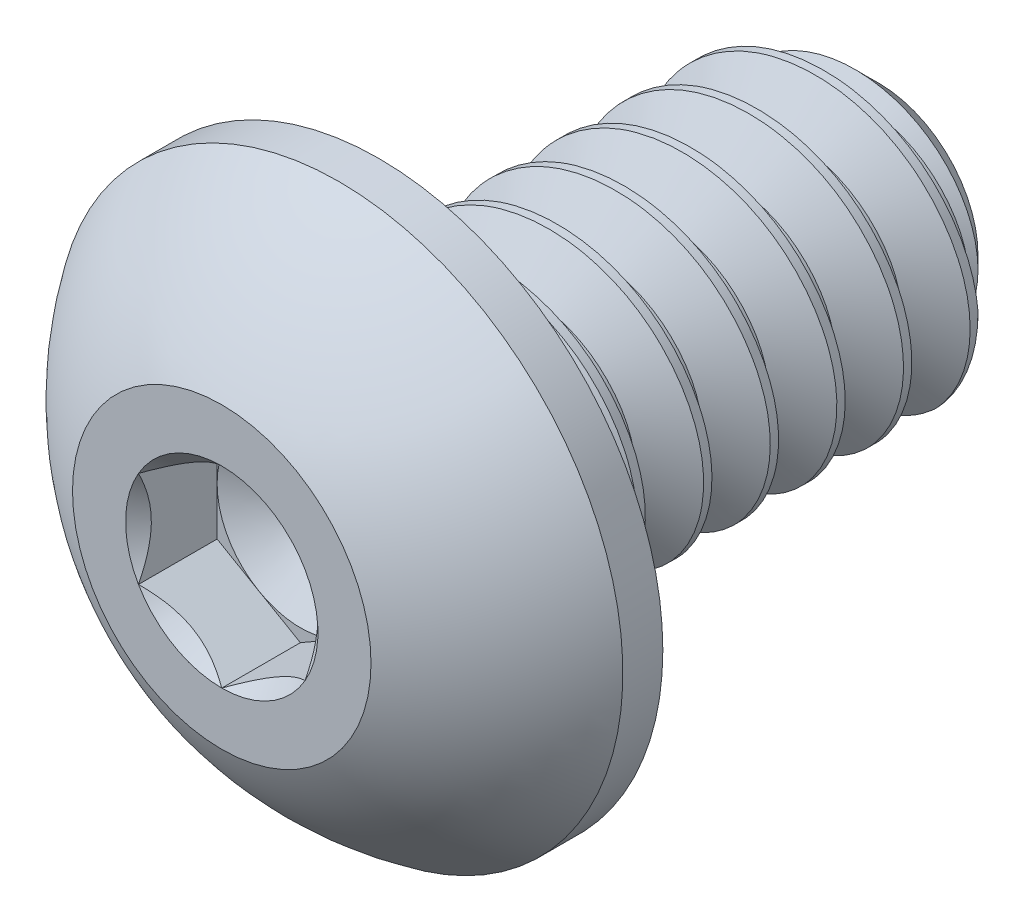
SolidWorks part; units mm, degrees
ref_plane "Front" through (0, 0, 0) normal (0, 0, 1) x (1, 0, 0)
ref_plane "Top" through (0, 0, 0) normal (0, 1, 0) x (1, 0, 0)
ref_plane "Right" through (0, 0, 0) normal (1, 0, 0) x (0, 0, -1)
sketch "Sketch1" plane through (0, 0, 0) normal (1, 0, 0) x (0, 0, -1)
  line L0 (0, 0) -> (-1.4986, 0) construction
  line L1 (0, 0) -> (4.7625, 0)
  line L2 (0, 0) -> (0, 1.4224)
  line L3 (0, 1.4224) -> (4.7625, 1.4224)
  line L4 (4.7625, 0) -> (4.7625, 1.4224)
  line L5 (0, -1.4224) -> (4.7625, -1.4224) construction
  dimension "D1" = 4.7625
  dimension "Thread Dia" = 2.8448
  dimension "Length" = 4.7625
  dimension "Head Height" = 1.4986
revolve "Revolve1" add sketch "Sketch1" angle 360 about L0
ref_plane "Plane1" through (0, 0, 1.4986) normal (0, 0, 1) x (1, 0, 0)
chamfer "Chamfer1" distance 0.4763 angle 45 1 edges at (0, 1.4224, -4.7625)
sketch "Sketch10" plane through (0, 0, 0) normal (1, 0, 0) x (0, 0, -1)
  line L0 (4.7625, 1.4224) -> (5.3181, 1.4224)
  line L1 (5.3181, 1.4224) -> (5.08, 1.01)
  line L2 (5.08, 1.01) -> (5.0006, 1.01)
  line L3 (5.0006, 1.01) -> (4.7625, 1.4224)
  line L4 (4.8816, 1.2162) -> (5.1991, 1.2162) construction
  dimension "D1" = 60
  dimension "D2" = 0.0794
  dimension "D3" = 0.3175
sketch "Sketch11" plane through (0, 0, -4.7625) normal (0, 0, -1) x (-1, 0, 0)
  circle A1 centre (0, 0) radius 0.9462
  circle A2 centre (0, 0) radius 0.9462
  dimension "D1" = 0
curve "Helix/Spiral1" pitch 0.635 height 7.9375 turns 12.5
sweep "Cut-Sweep1" cut profiles "Sketch10" path "Helix/Spiral1"
sketch "Sketch4" plane through (0, 0, 0) normal (0, 0, 1) x (1, 0, 0)
  circle A0 centre (0, 0) radius 2.7051
  dimension "Head Dia" = 5.4102
extrude "Extrude1" add sketch "Sketch4" along normal up to surface (1.4986 mm away) up to plane "Plane1"
sketch "Sketch9" plane through (0, 0, 0) normal (1, 0, 0) x (0, 0, -1)
  line L0 (0, 2.7051) -> (-0.381, 2.7051)
  line L1 (0, 2.7051) -> (0, 3.0861)
  line L2 (0, 3.0861) -> (-1.8796, 3.0861)
  line L3 (0, 0) -> (-1.4986, 0) construction
  line L4 (-1.8796, 3.0861) -> (-1.8796, 1.4224)
  line L5 (-1.8796, 1.4224) -> (-1.4986, 1.4224)
  line L6 (0, 0) -> (0, 1.4224) construction
  line L10 (0, 2.7051) -> (-1.4986, 2.7051) construction
  line L11 (0, 1.4224) -> (4.7625, 1.4224) construction
  line L12 (-1.4986, 2.7051) -> (-1.4986, -2.7051) construction
  arc A0 (-1.4986, 1.4224) -> (-0.381, 2.7051) centre (1.4288, 0) cw
  dimension "Side Head Height" = 0.381
revolve "Cut-Revolve3" cut sketch "Sketch9" angle 360 about L3
sketch "Sketch6" plane through (0, 0, 1.4986) normal (0, 0, 1) x (1, 0, 0)
  line L1 (0, -0.9165) -> (0.7937, -0.4583)
  line L2 (0.7937, -0.4583) -> (0.7937, 0.4583)
  line L3 (0.7937, 0.4583) -> (0, 0.9165)
  line L4 (0, 0.9165) -> (-0.7938, 0.4583)
  line L5 (-0.7938, 0.4583) -> (-0.7938, -0.4583)
  line L6 (-0.7938, -0.4583) -> (0, -0.9165)
  circle A0 centre (0, 0) radius 0.7938 construction
  dimension "Hex" = 1.5875
extrude "Cut-Extrude1" cut sketch "Sketch6" against normal blind 0.7493
sketch "Sketch7" plane through (0, 0, 1.4986) normal (0, 0, 1) x (1, 0, 0)
  circle A0 centre (0, 0) radius 0.9165
extrude "Cut-Extrude4" cut sketch "Sketch7" against normal blind 0.7493 draft 45
sketch "Sketch8" plane through (0, 0, 0.7493) normal (0, 0, 1) x (1, 0, 0)
  circle A0 centre (0, 0) radius 0.7938 construction
  circle A1 centre (0, 0) radius 0.7938
extrude "Cut-Extrude5" cut sketch "Sketch8" against normal blind 0.2498 draft 60
sketch "Sketch12" plane through (0, 0, 0) normal (1, 0, 0) x (0, 0, -1)
  line L1 (0, -1.4224) -> (4.7625, -1.4224) construction
  spline S0 degree 2 poles (4.2862, 0.013) (4.2444, 0.5945) (4.2069, 1.0058) (4.154, 1.5865) (4.101, 1.3739) (4.0481, 1.1614) (3.9952, 0.3681) (3.9423, -0.4251) (3.8894, -1.0058) (3.8365, -1.5865) (3.7835, -1.3739) (3.7306, -1.1614) (3.6777, -0.3681) (3.6248, 0.4251) (3.5719, 1.0058) (3.519, 1.5865) (3.466, 1.3739) (3.4131, 1.1614) (3.3602, 0.3681) (3.3073, -0.4251) (3.2544, -1.0058) (3.2015, -1.5865) (3.1485, -1.3739) (3.0956, -1.1614) (3.0427, -0.3681) (2.9898, 0.4251) (2.9369, 1.0058) (2.884, 1.5865) (2.831, 1.3739) (2.7781, 1.1614) (2.7252, 0.3681) (2.6723, -0.4251) (2.6194, -1.0058) (2.5665, -1.5865) (2.5135, -1.3739) (2.4606, -1.1614) (2.4077, -0.3681) (2.3548, 0.4251) (2.3019, 1.0058) (2.249, 1.5865) (2.196, 1.3739) (2.1431, 1.1614) (2.0902, 0.3681) (2.0373, -0.4251) (1.9844, -1.0058) (1.9315, -1.5865) (1.8785, -1.3739) (1.8256, -1.1614) (1.7727, -0.3681) (1.7198, 0.4251) (1.6669, 1.0058) (1.614, 1.5865) (1.561, 1.3739) (1.5081, 1.1614) (1.4552, 0.3681) (1.4023, -0.4251) (1.3494, -1.0058) (1.2965, -1.5865) (1.2435, -1.3739) (1.1906, -1.1614) (1.1377, -0.3681) (1.0848, 0.4251) (1.0319, 1.0058) (0.979, 1.5865) (0.926, 1.3739) (0.8731, 1.1614) (0.8202, 0.3681) (0.7673, -0.4251) (0.7144, -1.0058) (0.6615, -1.5865) (0.6085, -1.3739) (0.5556, -1.1614) (0.5027, -0.3681) (0.4498, 0.4251) (0.3969, 1.0058) (0.344, 1.5865) (0.291, 1.3739) (0.2381, 1.1614) (0.1852, 0.3681) (0.1323, -0.4251) (0.0794, -1.0058) (0.0419, -1.417) (0, -1.4223) knots 0.067474 0.067474 0.067474 0.076923 0.076923 0.089744 0.089744 0.102564 0.102564 0.115385 0.115385 0.128205 0.128205 0.141026 0.141026 0.153846 0.153846 0.166667 0.166667 0.179487 0.179487 0.192308 0.192308 0.205128 0.205128 0.217949 0.217949 0.230769 0.230769 0.24359 0.24359 0.25641 0.25641 0.269231 0.269231 0.282051 0.282051 0.294872 0.294872 0.307692 0.307692 0.320513 0.320513 0.333333 0.333333 0.346154 0.346154 0.358974 0.358974 0.371795 0.371795 0.384615 0.384615 0.397436 0.397436 0.410256 0.410256 0.423077 0.423077 0.435897 0.435897 0.448718 0.448718 0.461538 0.461538 0.474359 0.474359 0.487179 0.487179 0.5 0.5 0.512821 0.512821 0.525641 0.525641 0.538462 0.538462 0.551282 0.551282 0.564103 0.564103 0.576923 0.576923 0.586372 0.586372 0.586372 weights 0.948065 0.901259 1 0.866025 1 0.866025 1 0.866025 1 0.866025 1 0.866025 1 0.866025 1 0.866025 1 0.866025 1 0.866025 1 0.866025 1 0.866025 1 0.866025 1 0.866025 1 0.866025 1 0.866025 1 0.866025 1 0.866025 1 0.866025 1 0.866025 1 0.866025 1 0.866025 1 0.866025 1 0.866025 1 0.866025 1 0.866025 1 0.866025 1 0.866025 1 0.866025 1 0.866025 1 0.866025 1 0.866025 1 0.866025 1 0.866025 1 0.866025 1 0.866025 1 0.866025 1 0.866025 1 0.866025 1 0.866025 1 0.901259 0.948065 construction
  point P0 (3.8091, -1.4224)
equation "\"D1@Cut-Extrude1\"=\"Head Height@Sketch1\"/2"
equation "\"D1@Cut-Extrude4\"=\"D1@Cut-Extrude1\""
equation "\"D1@Cut-Extrude5\"=\"D1@Cut-Extrude1\"/3"
equation "\"D3@Helix/Spiral1\" = \"Length@Sketch1\" + .125"
equation "\"D1@Chamfer1\" = \"D4@Helix/Spiral1\" * .75"
equation "\"D2@Sketch10\" = \"D4@Helix/Spiral1\" * .125"
equation "\"D3@Sketch10\" = \"D4@Helix/Spiral1\" * .5"
